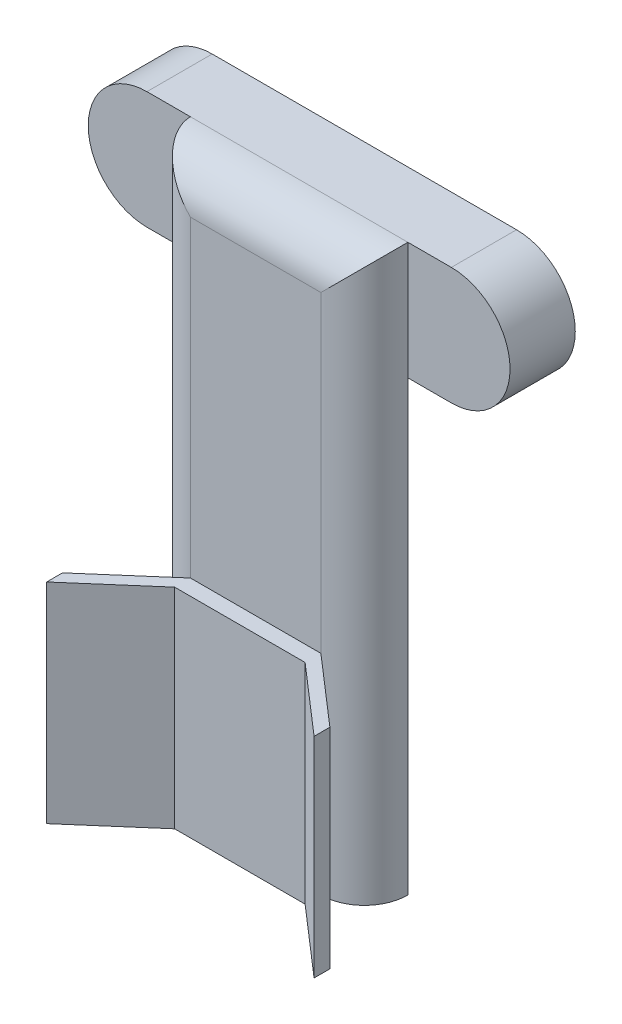
SolidWorks part; units mm, degrees
ref_plane "Front Plane" through (0, 0, 0) normal (0, 0, 1) x (1, 0, 0)
ref_plane "Top Plane" through (0, 0, 0) normal (0, 1, 0) x (1, 0, 0)
ref_plane "Right Plane" through (0, 0, 0) normal (1, 0, 0) x (0, 0, -1)
sketch "Sketch1" plane through (0, 0, 0) normal (0, 0, 1) x (1, 0, 0)
  line L0 (50, 212.065) -> (-20, 212.065) construction
  line L7 (50, 198.565) -> (-20, 198.565)
  line L8 (50, 225.565) -> (-20, 225.565)
  arc A0 (50, 198.565) -> (50, 225.565) centre (50, 212.065) ccw
  arc A1 (-20, 225.565) -> (-20, 198.565) centre (-20, 212.065) ccw
  point P0 (15, 178.465)
  point P7 (15, 212.065)
  dimension "D6" = 0
extrude "Extrude1" add sketch "Sketch1" along normal blind 15 contours L8 | L7 A0 L8 | L8 L7 | L8 A1 L7 | L7 region at (15, 212.065, 0)
sketch "Sketch2" plane through (0, 0, 15) normal (0, 0, 1) x (1, 0, 0)
  line L0 (50, 225.565) -> (-20, 225.565) construction
  line L1 (-10, 225.565) -> (40, 225.565)
  line L2 (-10, 225.565) -> (-10, 95.565)
  line L3 (-10, 95.565) -> (40, 95.565)
  line L4 (40, 225.565) -> (40, 95.565)
  dimension "D1" = 10
  dimension "D2" = 10
  dimension "D3" = 130
extrude "Extrude2" add sketch "Sketch2" along normal blind 10
fillet "Fillet1" radius 10 3 edges at (40, 160.565, 25) (-10, 160.565, 25) (15, 225.565, 25)
sketch "Sketch3" plane through (0, 0, 25) normal (0, 0, 1) x (1, 0, 0)
  line L0 (0, 215.565) -> (0, 95.565) construction
  line L1 (0, 143.6988) -> (30, 143.6988)
  line L2 (0, 143.6988) -> (0, 95.565)
  line L3 (0, 95.565) -> (30, 95.565)
  line L4 (30, 143.6988) -> (30, 95.565)
extrude "Extrude3" cut sketch "Sketch3" against normal blind 8
sketch "Sketch4" plane through (0, 143.6988, 0) normal (0, -1, 0) x (1, 0, 0)
  line L0 (30, 28.6318) -> (30, 25)
  line L1 (0, 17) -> (30, 17)
  line L2 (0, 17) -> (0, 25)
  line L3 (0, 25) -> (30, 25)
  line L4 (30, 17) -> (30, 25)
  line L5 (0, 25) -> (30, 25)
  line L6 (0, 25) -> (0, 28.6318)
  line L7 (0, 28.6318) -> (30, 28.6318)
  line L8 (30, 25) -> (30, 28.6318)
  line L9 (30, 28.6318) -> (45.7418, 42.308)
  line L10 (30, 25) -> (45.7418, 38.6762)
  line L11 (45.7418, 42.308) -> (45.7418, 38.6762)
  line L12 (15, 28.6318) -> (15, 25) construction
  line L13 (0, 28.6318) -> (0, 25)
  line L14 (0, 25) -> (-15.7418, 38.6762)
  line L15 (-15.7418, 42.308) -> (-15.7418, 38.6762)
  line L16 (0, 28.6318) -> (-15.7418, 42.308)
  line M1 (30, 25) -> (0, 25)
  line M2 (0, 25) -> (0, 17)
  line M3 (0, 17) -> (30, 17)
  line M4 (30, 17) -> (30, 25)
extrude "Extrude4" add sketch "Sketch4" along normal up to surface (48.1338 mm away) contours L5 M4 M1 M2 M3 | L7 L12 L0 M1 | L12 L7 L6 L5 | L6 L16 L15 L14 | L11 L9 L0 L10 region at (37.8709, 143.6988, 33.654) region at (22.5, 143.6988, 26.8159) region at (15, 143.6988, 21) region at (7.5, 143.6988, 26.8159) region at (-7.8709, 143.6988, 33.654) up to face at (15, 95.565, 19.6904)
